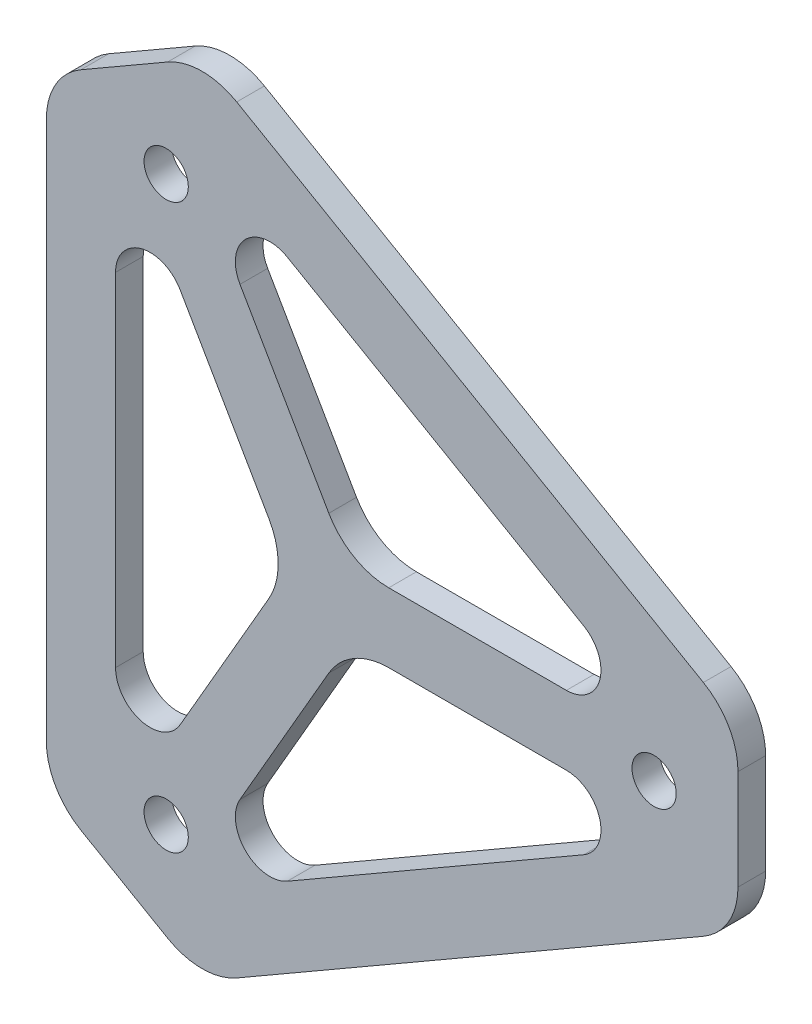
SolidWorks part; units mm, degrees
ref_plane "正面" through (0, 0, 0) normal (0, 0, 1) x (1, 0, 0)
ref_plane "平面" through (0, 0, 0) normal (0, 1, 0) x (1, 0, 0)
ref_plane "右側面" through (0, 0, 0) normal (1, 0, 0) x (0, 0, -1)
sketch "ｽｹｯﾁ1" plane through (0, 0, 0) normal (0, 0, 1) x (1, 0, 0)
  line L0 (-9.1562, 28.859) -> (-20.4145, 22.359)
  line L1 (23.5085, 0) -> (-11.7543, 20.359) construction
  line L2 (-11.7543, 20.359) -> (-11.7543, -20.359) construction
  line L3 (-11.7543, -20.359) -> (23.5085, 0) construction
  line L4 (29.5707, 6.5) -> (-9.1562, 28.859)
  line L5 (-20.4145, 22.359) -> (-20.4145, -22.359)
  line L6 (-9.1562, -28.859) -> (29.5707, -6.5)
  line L7 (-20.4145, -22.359) -> (-9.1562, -28.859)
  line L8 (29.5707, -6.5) -> (29.5707, 6.5)
  circle A0 centre (0, 0) radius 11.7543 construction
  circle A1 centre (-11.7543, 20.359) radius 1.6
  circle A2 centre (-11.7543, -20.359) radius 1.6
  circle A3 centre (23.5085, 0) radius 1.6
  circle A4 centre (0, 0) radius 20.4145 construction
  point P10 (40.829, 0)
  point P11 (-20.4145, 35.359)
  point P12 (-20.4145, -35.359)
  dimension "D2" = 3.2
  dimension "D3" = 3.2
  dimension "D4" = 3.2
  dimension "D1" = 40.718
  dimension "D5" = 70.718
extrude "ﾎﾞｽ - 押し出し1" add sketch "ｽｹｯﾁ1" along normal blind 2
sketch "ｽｹｯﾁ2" plane through (0, 0, 2) normal (0, 0, 1) x (1, 0, 0)
  line L12 (-12.2854, 21.2789) -> (0, 0)
  line L13 (0, 0) -> (-12.2854, -21.2789)
  line L14 (0, 0) -> (24.5707, 0)
  line L15 (0, -2.5) -> (24.5707, -2.5)
  line L16 (-14.4504, 20.0289) -> (-2.1651, -1.25)
  line L17 (-2.1651, 1.25) -> (-14.4504, -20.0289)
  line L18 (24.5707, 3.6132) -> (-9.1562, 23.0855)
  line L19 (-9.1562, 23.0855) -> (-15.4145, 19.4722)
  line L20 (-15.4145, 19.4722) -> (-15.4145, -19.4722)
  line L21 (-15.4145, -19.4722) -> (-9.1562, -23.0855)
  line L22 (-9.1562, -23.0855) -> (24.5707, -3.6132)
  line L23 (24.5707, -3.6132) -> (24.5707, 3.6132)
  line L24 (24.5707, 3.6132) -> (-9.1562, 23.0855)
  line L25 (-9.1562, 23.0855) -> (-15.4145, 19.4722)
  line L26 (-15.4145, 19.4722) -> (-15.4145, -19.4722)
  line L27 (-15.4145, -19.4722) -> (-9.1562, -23.0855)
  line L28 (-9.1562, -23.0855) -> (24.5707, -3.6132)
  line L29 (24.5707, -3.6132) -> (24.5707, 3.6132)
  line L30 (0, 2.5) -> (24.5707, 2.5)
  line L31 (-10.1203, 22.5289) -> (2.1651, 1.25)
  line L32 (2.1651, -1.25) -> (-10.1203, -22.5289)
  dimension "D1" = 5
  dimension "D2" = 2.5
  dimension "D3" = 2.5
extrude "ｶｯﾄ - 押し出し1" cut sketch "ｽｹｯﾁ2" against normal blind 10 contours L16 L26 L17 | L15 L32 L28 | L24 L31 L30 region at (5.604, 9.7063, 2) region at (-11.2079, 0, 2) region at (5.604, -9.7063, 2)
fillet "ﾌｨﾚｯﾄ1" radius 5 15 edges at (1.4434, 2.5, 1) (1.4434, -2.5, 1) (-2.8868, 0, 1) (29.5707, -6.5, 1) (29.5707, 6.5, 1) (-9.1562, 28.859, 1) (-20.4145, 22.359, 1) (-20.4145, -22.359, 1) (-9.1562, -28.859, 1) (-14.4504, -20.0289, 1) (-10.1203, -22.5289, 1) (24.5707, -2.5, 1) (24.5707, 2.5, 1) (-10.1203, 22.5289, 1) (-14.4504, 20.0289, 1)
fillet "ﾌｨﾚｯﾄ2" radius 2.5 6 edges at (-15.4145, -19.4722, 1) (-9.1562, -23.0855, 1) (-15.4145, 19.4722, 1) (-9.1562, 23.0855, 1) (24.5707, -3.6132, 1) (24.5707, 3.6132, 1)
